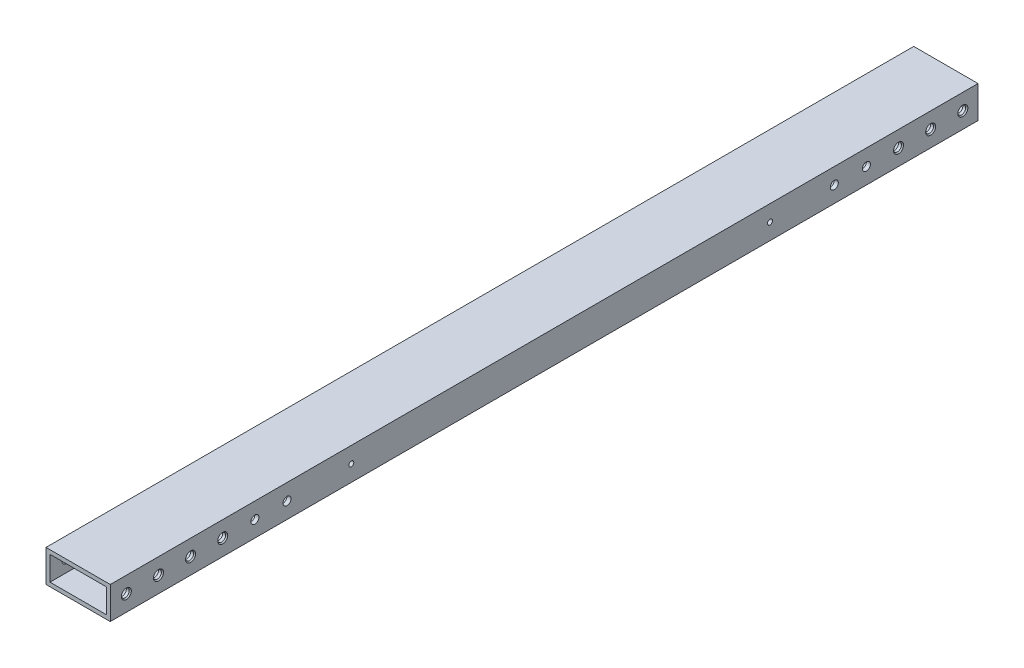
SolidWorks part; units mm, degrees
material "6061 Alloy"
ref_plane "Front Plane" through (0, 0, 0) normal (0, 0, 1) x (1, 0, 0)
ref_plane "Top Plane" through (0, 0, 0) normal (0, 1, 0) x (1, 0, 0)
ref_plane "Right Plane" through (0, 0, 0) normal (1, 0, 0) x (0, 0, -1)
sketch "Sketch1" plane through (0, 0, 0) normal (0, 0, 1) x (1, 0, 0)
  line L0 (-22.225, 9.525) -> (22.225, 9.525)
  line L2 (-25.4, 12.7) -> (25.4, 12.7)
  line L3 (-25.4, 12.7) -> (-25.4, -12.7)
  line L4 (-25.4, -12.7) -> (25.4, -12.7)
  line L5 (25.4, 12.7) -> (25.4, -12.7)
  line L10 (22.225, 9.525) -> (22.225, -9.525)
  line L11 (-22.225, -9.525) -> (22.225, -9.525)
  line L12 (-22.225, 9.525) -> (-22.225, -9.525)
  point P12 (0, 12.7)
  point P14 (25.4, 0)
  dimension "Wall Thickness" = 3.175
  dimension "Outside Width" = 50.8
  dimension "Outside Height" = 25.4
  dimension "Inside Height" = 19.05
  dimension "Inside Width" = 44.45
sketch "Sketch2" plane through (0, 0, 0) normal (1, 0, 0) x (0, 0, -1)
  line L0 (342.9, 0) -> (-342.9, 0)
  point P4 (0, 0)
  point P7 (-342.9, 0)
  point P10 (342.9, 0)
  dimension "Length" = 685.8
sketch "Sketch3" plane through (0, 0, 0) normal (0, 0, 1) x (1, 0, 0)
  line L21 (25.4, 12.7) -> (-25.4, 12.7)
  line L22 (25.4, -12.7) -> (25.4, 12.7)
  line L23 (-25.4, -12.7) -> (25.4, -12.7)
  line L24 (-25.4, 12.7) -> (-25.4, -12.7)
  line L25 (25.4, 12.7) -> (-25.4, 12.7)
  line L26 (25.4, -12.7) -> (25.4, 12.7)
  line L27 (-25.4, -12.7) -> (25.4, -12.7)
  line L28 (-25.4, 12.7) -> (-25.4, -12.7)
  line L29 (22.225, 9.525) -> (-22.225, 9.525)
  line L30 (22.225, -9.525) -> (22.225, 9.525)
  line L31 (-22.225, -9.525) -> (22.225, -9.525)
  line L32 (-22.225, 9.525) -> (-22.225, -9.525)
  line L33 (22.225, 9.525) -> (-22.225, 9.525)
  line L34 (22.225, -9.525) -> (22.225, 9.525)
  line L35 (-22.225, -9.525) -> (22.225, -9.525)
  line L36 (-22.225, 9.525) -> (-22.225, -9.525)
  dimension "D1" = 0
  dimension "D2" = 0
extrude "Boss-Extrude1" add sketch "Sketch3" along normal up to vertex (342.9 mm away) and the other way up to vertex (342.9 mm away) up to point (0, 0, 342.9) other way up to point (0, 0, -342.9)
sketch "Drawing Reference" plane through (0, 0, 0) normal (1, 0, 0) x (0, 0, -1)
  line L0 (-342.9, 0) -> (342.9, 0) construction
  line L1 (0, -12.7) -> (0, 12.7) construction
  line L2 (-342.9, -12.7) -> (342.9, -12.7) construction
  line L5 (-342.9, 12.7) -> (342.9, 12.7) construction
  point P7 (-306.324, 0)
  point P8 (306.324, 0)
  dimension "D1" = 36.576
sketch "Sketch5" plane through (25.4, 0, 0) normal (1, 0, 0) x (0, 0, -1)
  line L0 (-342.9, 0) -> (-279.4, 0)
  line L1 (-342.9, -12.7) -> (-342.9, 12.7) construction
  line L2 (-279.4, 0) -> (-254, 0)
  line L3 (-254, 0) -> (-228.6, 0)
  line L4 (-228.6, 0) -> (-203.2, 0)
sketch "Sketch8" plane through (25.4, 0, 0) normal (1, 0, 0) x (0, 0, -1)
  line L0 (342.9, 0) -> (305.5118, 0)
  line L1 (342.9, -12.7) -> (342.9, 12.7) construction
  line L2 (305.5118, 0) -> (280.1118, 0)
  line L3 (280.1118, 0) -> (254.7118, 0)
  line L4 (254.7118, 0) -> (229.3118, 0)
hole_wizard "1/4 (0.25) Diameter Hole3" positions "Sketch12" profile "Sketch13" hole size "1/4" standard "ANSI Inch" end condition through all
sketch "Sketch12" plane through (-25.4, 0, 0) normal (-1, 0, 0) x (0, 0, 1)
  point P0 (-330.9118, 0)
sketch "Sketch13" plane through (-25.4, 0, -330.9118) normal (0, 1, 0) x (0, 0, 1)
  line L0 (0, 0) -> (0, 50.8)
  line L1 (0, 50.8) -> (3.9624, 50.8)
  line L2 (3.175, 49.8942) -> (3.175, 0)
  line L5 (3.175, 0) -> (0, 0)
  line L7 (3.9624, 50.8) -> (3.175, 49.8942)
  line L8 (-3.9624, 50.8) -> (-3.175, 49.8942) construction
  line L11 (0, -6.35) -> (0, 107.95) construction
  dimension "Thru Hole Dia." = 6.35
  dimension "Thru Hole Depth" = 50.8
  dimension "Far C'Sink Dia." = 7.9248
  dimension "Far C'Sink Angle" = 82
hole_wizard "1/4 (0.25) Diameter Hole4" positions "Sketch14" profile "Sketch15" hole size "1/4" standard "ANSI Inch" end condition through all
sketch "Sketch14" plane through (-25.4, 0, 0) normal (-1, 0, 0) x (0, 0, 1)
  point P0 (304.8, 0)
  point P3 (330.2, 0)
sketch "Sketch15" plane through (-25.4, 0, 304.8) normal (0, 1, 0) x (0, 0, 1)
  line L0 (0, 0) -> (0, 50.8)
  line L1 (0, 50.8) -> (3.9624, 50.8)
  line L2 (3.175, 49.8942) -> (3.175, 0)
  line L5 (3.175, 0) -> (0, 0)
  line L7 (3.9624, 50.8) -> (3.175, 49.8942)
  line L8 (-3.9624, 50.8) -> (-3.175, 49.8942) construction
  line L11 (0, -6.35) -> (0, 107.95) construction
  dimension "Thru Hole Dia." = 6.35
  dimension "Thru Hole Depth" = 50.8
  dimension "Far C'Sink Dia." = 7.9248
  dimension "Far C'Sink Angle" = 82
hole_wizard "1/4 (0.25) Diameter Hole5" positions "Sketch17" profile "Sketch18" hole size "1/4" standard "ANSI Inch" end condition through all
sketch "Sketch17" plane through (25.4, 0, 0) normal (1, 0, 0) x (0, 0, -1)
  point P0 (305.5118, 0)
  point P3 (280.1118, 0)
sketch "Sketch18" plane through (25.4, 0, -305.5118) normal (0, 1, 0) x (0, 0, -1)
  line L0 (0, 0) -> (0, 50.8)
  line L1 (0, 50.8) -> (3.175, 50.8)
  line L2 (3.175, 50.8) -> (3.175, 0.9058)
  line L3 (3.175, 0.9058) -> (3.9624, 0)
  line L5 (3.9624, 0) -> (0, 0)
  line L6 (-3.175, 0.9058) -> (-3.9624, 0) construction
  line L11 (0, -6.35) -> (0, 107.95) construction
  dimension "Thru Hole Dia." = 6.35
  dimension "Thru Hole Depth" = 50.8
  dimension "Near C'Sink Dia." = 7.9248
  dimension "Near C'Sink Angle" = 82
hole_wizard "1/4 (0.25) Diameter Hole6" positions "Sketch19" profile "Sketch20" hole size "1/4" standard "ANSI Inch" end condition through all
sketch "Sketch19" plane through (25.4, 0, 0) normal (1, 0, 0) x (0, 0, -1)
  point P0 (229.3118, 0)
  point P3 (254.7118, 0)
sketch "Sketch20" plane through (25.4, 0, -229.3118) normal (0, 1, 0) x (0, 0, -1)
  line L0 (0, 0) -> (0, 50.8)
  line L1 (0, 50.8) -> (3.175, 50.8)
  line L2 (3.175, 50.8) -> (3.175, 0)
  line L5 (3.175, 0) -> (0, 0)
  line L11 (0, -6.35) -> (0, 107.95) construction
  dimension "Thru Hole Dia." = 6.35
  dimension "Thru Hole Depth" = 50.8
hole_wizard "1/4 (0.25) Diameter Hole7" positions "Sketch21" profile "Sketch22" hole size "1/4" standard "ANSI Inch" end condition through all
sketch "Sketch21" plane through (25.4, 0, 0) normal (1, 0, 0) x (0, 0, -1)
  point P0 (-203.2, 0)
  point P3 (-228.6, 0)
sketch "Sketch22" plane through (25.4, 0, 203.2) normal (0, 1, 0) x (0, 0, -1)
  line L0 (0, 0) -> (0, 50.8)
  line L1 (0, 50.8) -> (3.175, 50.8)
  line L2 (3.175, 50.8) -> (3.175, 0)
  line L5 (3.175, 0) -> (0, 0)
  line L11 (0, -6.35) -> (0, 107.95) construction
  dimension "Thru Hole Dia." = 6.35
  dimension "Thru Hole Depth" = 50.8
hole_wizard "1/4 (0.25) Diameter Hole8" positions "Sketch23" profile "Sketch24" hole size "1/4" standard "ANSI Inch" end condition through all
sketch "Sketch23" plane through (25.4, 0, 0) normal (1, 0, 0) x (0, 0, -1)
  point P0 (-279.4, 0)
  point P3 (-254, 0)
sketch "Sketch24" plane through (25.4, 0, 279.4) normal (0, 1, 0) x (0, 0, -1)
  line L0 (0, 0) -> (0, 50.8)
  line L1 (0, 50.8) -> (3.175, 50.8)
  line L2 (3.175, 50.8) -> (3.175, 0.9058)
  line L3 (3.175, 0.9058) -> (3.9624, 0)
  line L5 (3.9624, 0) -> (0, 0)
  line L6 (-3.175, 0.9058) -> (-3.9624, 0) construction
  line L11 (0, -6.35) -> (0, 107.95) construction
  dimension "Thru Hole Dia." = 6.35
  dimension "Thru Hole Depth" = 50.8
  dimension "Near C'Sink Dia." = 7.9248
  dimension "Near C'Sink Angle" = 82
sketch "Sketch25" plane through (25.4, 0, 0) normal (1, 0, 0) x (0, 0, -1)
  line L0 (-203.2, 0) -> (-152.4, 0)
  line L1 (229.3118, 0) -> (178.5118, 0)
hole_wizard "5/32 (0.15625) Diameter Hole1" positions "Sketch26" profile "Sketch27" hole size "5/32" standard "ANSI Inch" end condition through all
sketch "Sketch26" plane through (25.4, 0, 0) normal (1, 0, 0) x (0, 0, -1)
  point P0 (-152.4, 0)
  point P3 (178.5118, 0)
sketch "Sketch27" plane through (25.4, 0, 152.4) normal (0, 1, 0) x (0, 0, -1)
  line L0 (0, 0) -> (0, 50.8)
  line L1 (0, 50.8) -> (1.9844, 50.8)
  line L2 (1.9844, 50.8) -> (1.9844, 0)
  line L5 (1.9844, 0) -> (0, 0)
  line L11 (0, -6.35) -> (0, 107.95) construction
  dimension "Thru Hole Dia." = 3.9688
  dimension "Thru Hole Depth" = 50.8
equation "\"D1@Drawing Reference\"=\"Outside Width@Sketch1\" * 0.72"
